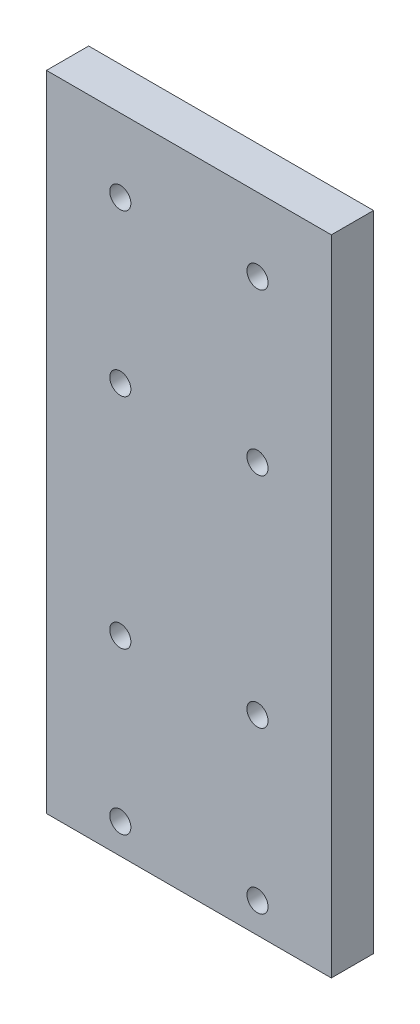
SolidWorks part; units mm, degrees
ref_plane "Front Plane" through (0, 0, 0) normal (0, 0, 1) x (1, 0, 0)
ref_plane "Top Plane" through (0, 0, 0) normal (0, 1, 0) x (1, 0, 0)
ref_plane "Right Plane" through (0, 0, 0) normal (1, 0, 0) x (0, 0, -1)
sketch "Sketch1" plane through (0, 0, 0) normal (0, 0, 1) x (1, 0, 0)
  line L0 (0, 61) -> (0, -61) construction
  line L1 (-27, -61) -> (27, -61)
  line L2 (-27, -61) -> (-27, 61)
  line L3 (-27, 61) -> (27, 61)
  line L4 (27, -61) -> (27, 61)
  line L5 (-27, -61) -> (27, 61) construction
  line L6 (-27, 61) -> (27, -61) construction
  line L7 (-27, -40.05) -> (0, -40.05) construction
  line L8 (-27, 31.89) -> (0, 31.89) construction
  line L10 (-13, 16.64) -> (13, 16.64) construction
  line L11 (-13, 16.64) -> (-13, 47.14) construction
  line L12 (-13, 47.14) -> (13, 47.14) construction
  line L13 (13, 16.64) -> (13, 47.14) construction
  line L14 (-13, 16.64) -> (13, 47.14) construction
  line L15 (-13, 47.14) -> (13, 16.64) construction
  line L16 (-13, -55.3) -> (13, -55.3) construction
  line L17 (-13, -55.3) -> (-13, -24.8) construction
  line L18 (-13, -24.8) -> (13, -24.8) construction
  line L19 (13, -55.3) -> (13, -24.8) construction
  line L20 (-13, -55.3) -> (13, -24.8) construction
  line L21 (-13, -24.8) -> (13, -55.3) construction
  circle A0 centre (-13, 47.14) radius 2
  circle A1 centre (13, 47.14) radius 2
  circle A2 centre (13, 16.64) radius 2
  circle A3 centre (-13, 16.64) radius 2
  circle A4 centre (13, -24.8) radius 2
  circle A5 centre (-13, -24.8) radius 2
  circle A6 centre (-13, -55.3) radius 2
  circle A7 centre (13, -55.3) radius 2
  point P0 (0, 0)
  dimension "D1" = 122
  dimension "D2" = 54
  dimension "D3" = 71.94
  dimension "D4" = 5.7
  dimension "D5" = 26
  dimension "D6" = 30.5
  dimension "D7" = 26
  dimension "D8" = 30.5
extrude "Boss-Extrude1" add sketch "Sketch1" along normal blind 8
